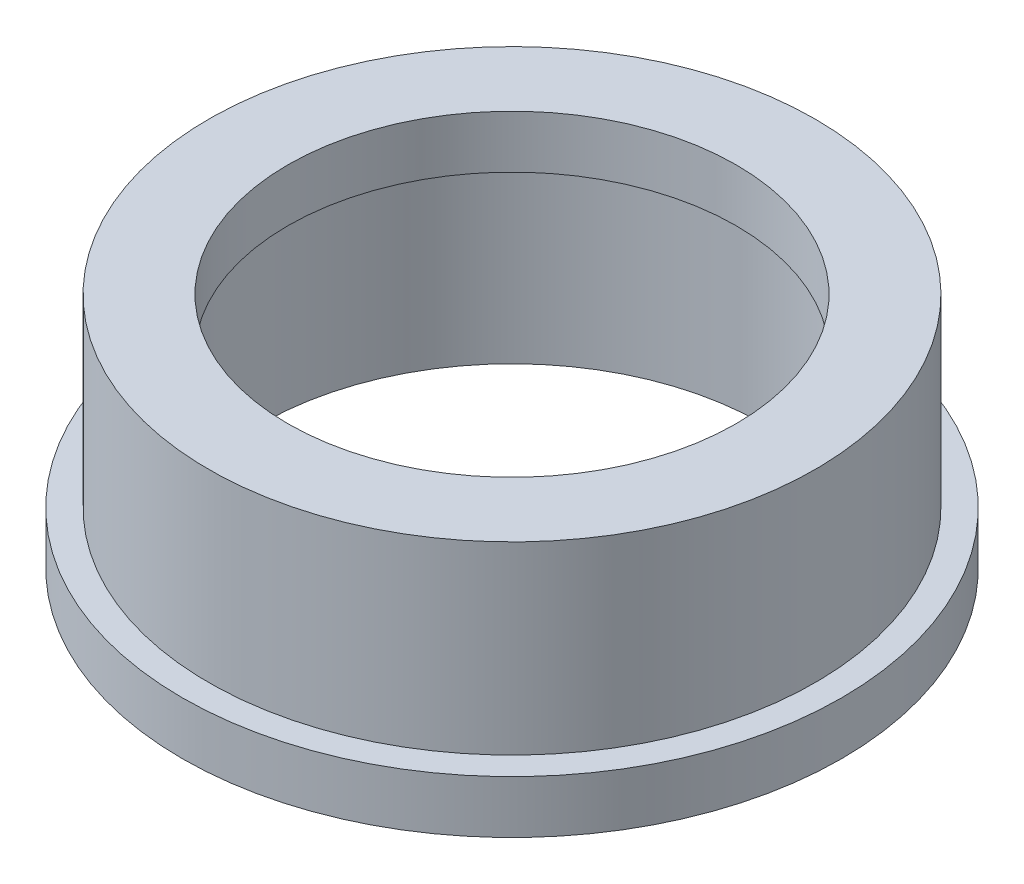
SolidWorks part; units mm, degrees
material "Сталь ШХ15 ГОСТ 801-78"
ref_plane "Plane1" through (0, 0, 0) normal (0, 0, 1) x (1, 0, 0)
ref_plane "Plane2" through (0, 0, 0) normal (0, 1, 0) x (1, 0, 0)
ref_plane "Plane3" through (0, 0, 0) normal (1, 0, 0) x (0, 0, -1)
sketch "Эскиз1" plane through (0, 0, 0) normal (0, 0, 1) x (1, 0, 0)
  line L0 (0, 0) -> (0, 42.3011) construction
  line L1 (9.5, 7) -> (9.5, 0)
  line L2 (9.5, 0) -> (12.5, 0)
  line L3 (12.5, 0) -> (12.5, 2)
  line L4 (12.5, 2) -> (11.5, 2)
  line L5 (11.5, 2) -> (11.5, 9)
  line L6 (11.5, 9) -> (8.5, 9)
  line L7 (8.5, 9) -> (8.5, 7)
  line L8 (8.5, 7) -> (9.5, 7)
  dimension "D1" = 9.5
  dimension "D2" = 5
  dimension "D3" = 2
  dimension "D4" = 1
  dimension "D5" = 3
revolve "Повернуть1" add sketch "Эскиз1" angle 360 about L0
